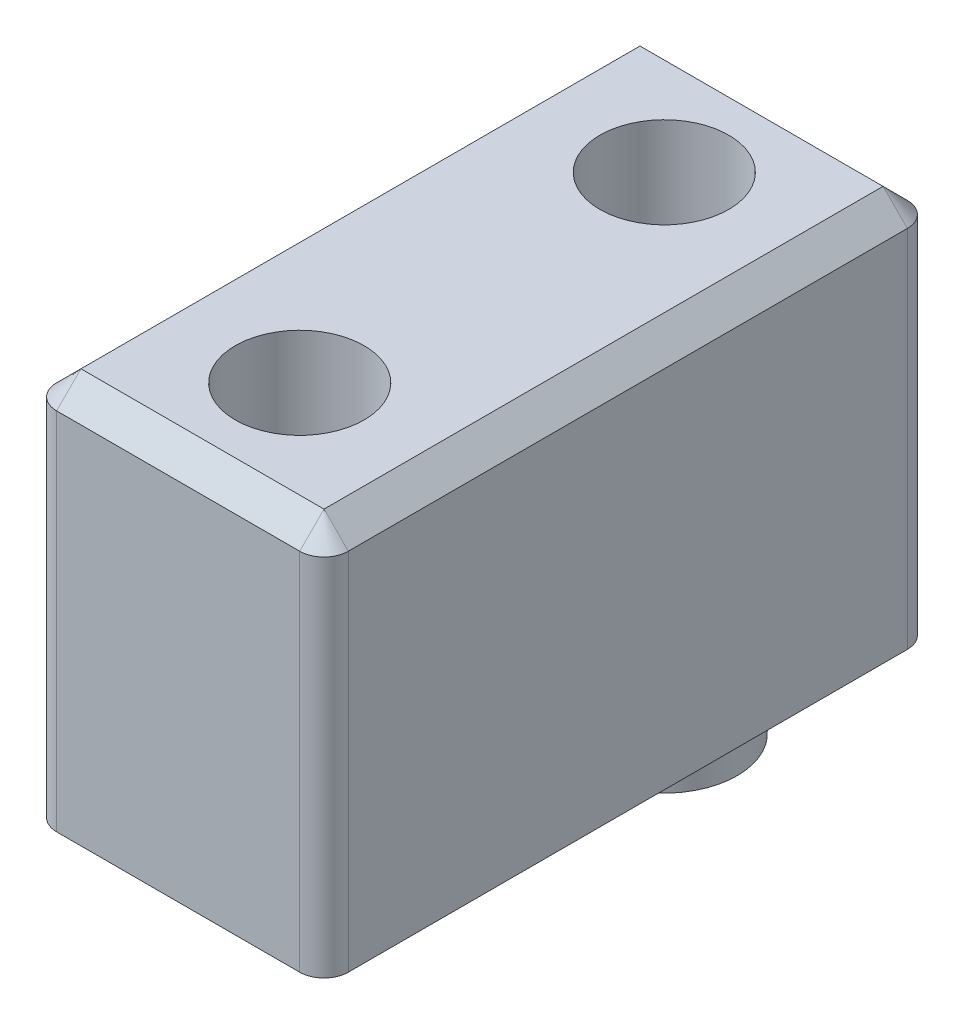
SolidWorks part; units mm, degrees
ref_plane "Front Plane" through (0, 0, 0) normal (0, 0, 1) x (1, 0, 0)
ref_plane "Top Plane" through (0, 0, 0) normal (0, 1, 0) x (1, 0, 0)
ref_plane "Right Plane" through (0, 0, 0) normal (1, 0, 0) x (0, 0, -1)
sketch "Sketch1" plane through (0, 0, 0) normal (0, 1, 0) x (1, 0, 0)
  line L0 (0, 7.5) -> (0, -7.5) construction
  line L1 (-6, 12.5) -> (6, 12.5)
  line L2 (-6, 12.5) -> (-6, -12.5)
  line L3 (-6, -12.5) -> (6, -12.5)
  line L4 (6, 12.5) -> (6, -12.5)
  line L5 (-6, 12.5) -> (6, -12.5) construction
  line L6 (-6, -12.5) -> (6, 12.5) construction
  circle A0 centre (0, 7.5) radius 2.65
  circle A1 centre (0, -7.5) radius 2.65
  point P0 (0, 0)
  dimension "D2" = 5.3
  dimension "D3" = 15
  dimension "D5" = 5.3
  dimension "D1" = 25
  dimension "D4" = 12
extrude "Boss-Extrude1" add sketch "Sketch1" along normal mid plane 16
sketch "Sketch2" plane through (0, -8, 0) normal (0, -1, 0) x (1, 0, 0)
  circle A0 centre (0, -7.5) radius 3
  circle A1 centre (0, -7.5) radius 2.5
  dimension "D1" = 6
  dimension "D2" = 5
extrude "Boss-Extrude2" add sketch "Sketch2" along normal blind 4
fillet "Fillet1" radius 1 4 edges at (-6, 0, 12.5) (-6, 0, -12.5) (6, 0, -12.5) (6, 0, 12.5)
chamfer "Chamfer1" distance 1 angle 45 8 edges at (0, 8, -12.5) (-5.7071, 8, -12.2071) (5.7071, 8, -12.2071) (-6, 8, 0) (6, 8, 0) (-5.7071, 8, 12.2071) (5.7071, 8, 12.2071) (0, 8, 12.5)
